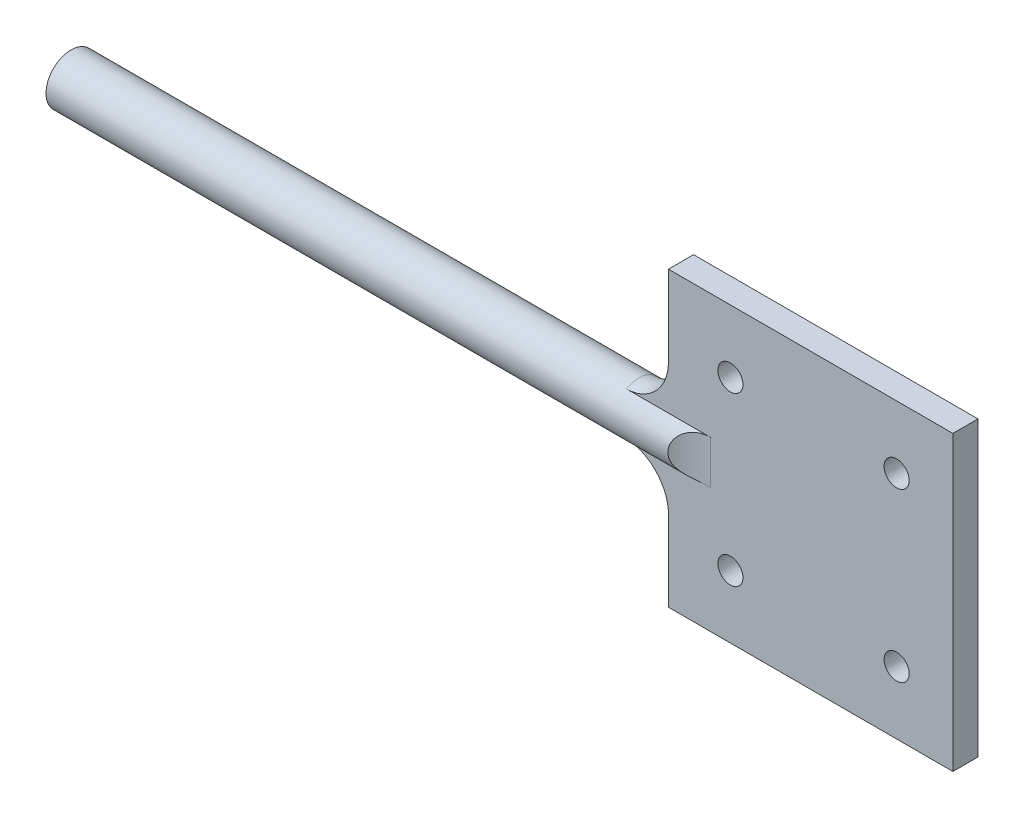
SolidWorks part; units mm, degrees
ref_plane "前视基准面" through (0, 0, 0) normal (0, 0, 1) x (1, 0, 0)
ref_plane "上视基准面" through (0, 0, 0) normal (0, 1, 0) x (1, 0, 0)
ref_plane "右视基准面" through (0, 0, 0) normal (1, 0, 0) x (0, 0, -1)
sketch "草图1" plane through (0, 0, 0) normal (0, 0, 1) x (1, 0, 0)
  line L1 (17, -17.5) -> (-17, -17.5)
  line L2 (17, -17.5) -> (17, 17.5)
  line L3 (17, 17.5) -> (-17, 17.5)
  line L4 (-17, -17.5) -> (-17, 17.5)
  line L5 (17, -17.5) -> (-17, 17.5) construction
  line L6 (17, 17.5) -> (-17, -17.5) construction
  point P0 (0, 0)
  dimension "D1" = 35
  dimension "D2" = 34
extrude "凸台-拉伸1" add sketch "草图1" along normal blind 3
sketch "草图7" plane through (0, 0, 3) normal (0, 0, 1) x (1, 0, 0)
  circle A0 centre (10.2752, 10) radius 1.5
  circle A1 centre (10.2752, -10) radius 1.5
  circle A2 centre (-9.5936, 10) radius 1.5
  circle A3 centre (-9.5936, -10) radius 1.5
  dimension "D1" = 10
  dimension "D2" = 10
  dimension "D3" = 10
  dimension "D5" = 3
  dimension "D4" = 10
extrude "切除-拉伸1" cut sketch "草图7" against normal blind 10
sketch "草图8" plane through (-17, 0, 0) normal (-1, 0, 0) x (0, 0, 1)
  line L0 (0, 0) -> (3, 0) construction
  line L1 (0, 17.5) -> (0, -17.5) construction
  line L2 (3, 17.5) -> (3, -17.5) construction
  circle A0 centre (1.5, 0) radius 3
  dimension "D1" = 6
extrude "凸台-拉伸2" add sketch "草图8" along normal blind 72.9
fillet "圆角1" radius 5 1 edges at (-17, 0, 3)
fillet "圆角2" radius 5 1 edges at (-17, -3, 1.5)
fillet "圆角3" radius 5 1 edges at (-17, 3, 1.5)
